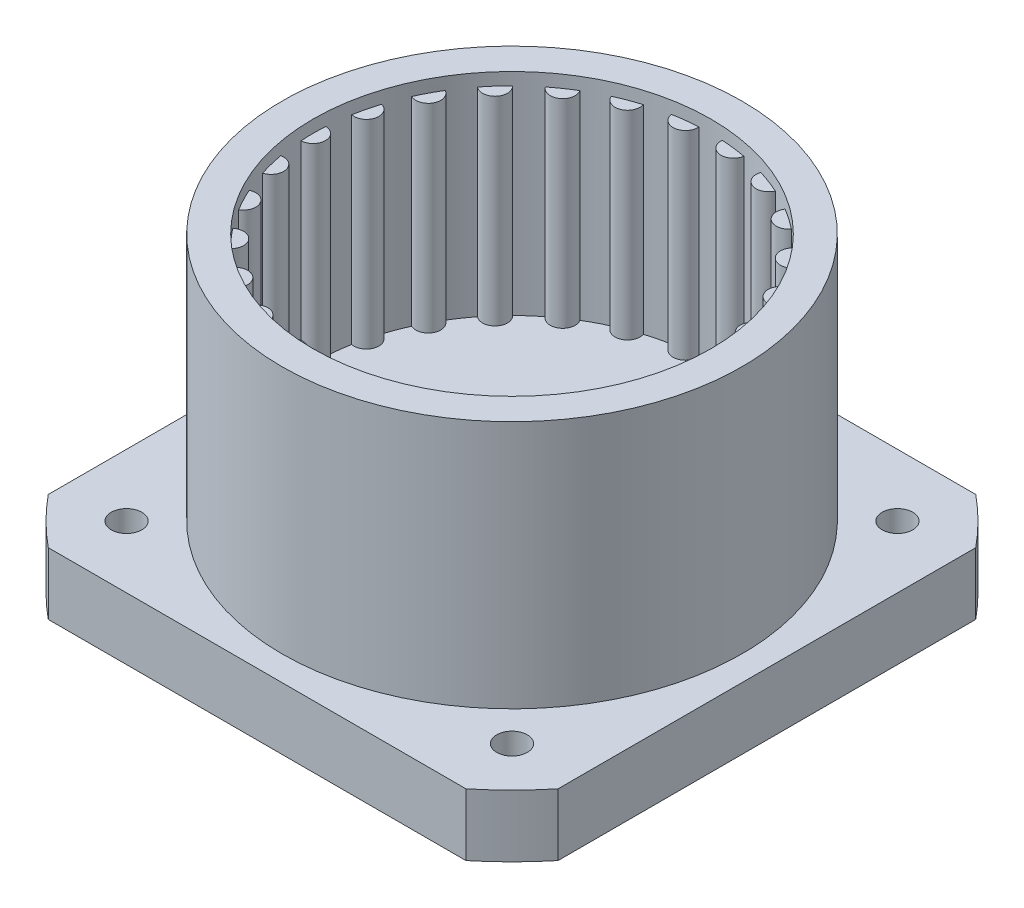
SolidWorks part; units mm, degrees
ref_plane "Front Plane" through (0, 0, 0) normal (0, 0, 1) x (1, 0, 0)
ref_plane "Top Plane" through (0, 0, 0) normal (0, 1, 0) x (1, 0, 0)
ref_plane "Right Plane" through (0, 0, 0) normal (1, 0, 0) x (0, 0, -1)
sketch "Sketch1" plane through (0, 0, 0) normal (0, 1, 0) x (1, 0, 0)
  circle A0 centre (15.5, 0) radius 1
  circle A1 centre (15.0351, -3.8291) radius 1
  circle A2 centre (13.6673, -7.4356) radius 1
  circle A3 centre (11.4762, -10.61) radius 1
  circle A4 centre (8.589, -13.1677) radius 1
  circle A5 centre (5.1737, -14.9603) radius 1
  circle A6 centre (1.4286, -15.8833) radius 1
  circle A7 centre (-2.4286, -15.8833) radius 1
  circle A8 centre (-6.1737, -14.9603) radius 1
  circle A9 centre (-9.589, -13.1677) radius 1
  circle A10 centre (-12.4762, -10.61) radius 1
  circle A11 centre (-14.6673, -7.4356) radius 1
  circle A12 centre (-16.0351, -3.8291) radius 1
  circle A13 centre (-16.5, 0) radius 1
  circle A14 centre (-16.0351, 3.8291) radius 1
  circle A15 centre (-14.6673, 7.4356) radius 1
  circle A16 centre (-12.4762, 10.61) radius 1
  circle A17 centre (-9.589, 13.1677) radius 1
  circle A18 centre (-6.1737, 14.9603) radius 1
  circle A19 centre (-2.4286, 15.8833) radius 1
  circle A20 centre (1.4286, 15.8833) radius 1
  circle A21 centre (5.1737, 14.9603) radius 1
  circle A22 centre (8.589, 13.1677) radius 1
  circle A23 centre (11.4762, 10.61) radius 1
  circle A24 centre (13.6673, 7.4356) radius 1
  circle A25 centre (15.0351, 3.8291) radius 1
  spline S0 degree 4 number of poles 315 (14.4, 0) -> (-15.4, 0) construction
sketch "Sketch2" plane through (0, 0, 0) normal (0, 1, 0) x (1, 0, 0)
  circle A0 centre (15.5, 0) radius 1
  circle A1 centre (15.0351, -3.8291) radius 1
  circle A2 centre (13.6673, -7.4356) radius 1
  circle A3 centre (11.4762, -10.61) radius 1
  circle A4 centre (8.589, -13.1677) radius 1
  circle A5 centre (5.1737, -14.9603) radius 1
  circle A6 centre (1.4286, -15.8833) radius 1
  circle A7 centre (-2.4286, -15.8833) radius 1
  circle A8 centre (-6.1737, -14.9603) radius 1
  circle A9 centre (-9.589, -13.1677) radius 1
  circle A10 centre (-12.4762, -10.61) radius 1
  circle A11 centre (-14.6673, -7.4356) radius 1
  circle A12 centre (-16.0351, -3.8291) radius 1
  circle A13 centre (-16.5, 0) radius 1
  circle A14 centre (-16.0351, 3.8291) radius 1
  circle A15 centre (-14.6673, 7.4356) radius 1
  circle A16 centre (-12.4762, 10.61) radius 1
  circle A17 centre (-9.589, 13.1677) radius 1
  circle A18 centre (-6.1737, 14.9603) radius 1
  circle A19 centre (-2.4286, 15.8833) radius 1
  circle A20 centre (1.4286, 15.8833) radius 1
  circle A21 centre (5.1737, 14.9603) radius 1
  circle A22 centre (8.589, 13.1677) radius 1
  circle A23 centre (11.4762, 10.61) radius 1
  circle A24 centre (13.6673, 7.4356) radius 1
  circle A25 centre (15.0351, 3.8291) radius 1
extrude "Boss-Extrude1" add sketch "Sketch2" along normal blind 8 and the other way blind 8
sketch "Sketch4" plane through (0, 0, 0) normal (0, 1, 0) x (1, 0, 0)
  line L0 (-15.4, 0) -> (14.4, 0) construction
  line L1 (0, 0) -> (0, 14.9128) construction
  line L2 (0, 0) -> (0, -14.9128) construction
  line L3 (0, 0) -> (-0.5, 0) construction
  line L4 (-0.5, 0) -> (-0.5, 15.3103) construction
  line L5 (-0.5, 0) -> (-0.5, -15.3103) construction
  line L6 (14.4, 0) -> (15.5, 0) construction
  line L7 (0, 0) -> (10, 0) construction
  line L8 (7.9, 0) -> (9.5, 0)
  line L9 (-0.5, 0) -> (9.5, 0) construction
  line L10 (-0.5, 15.3103) -> (-0.5, -15.3103) construction
  circle A0 centre (-0.5, 0) radius 16
  circle A1 centre (15.5, 0) radius 1
  circle A2 centre (15.0351, -3.8291) radius 1
  circle A3 centre (13.6673, -7.4356) radius 1
  circle A4 centre (11.4762, -10.61) radius 1
  circle A5 centre (8.589, -13.1677) radius 1
  circle A6 centre (5.1737, -14.9603) radius 1
  circle A7 centre (1.4286, -15.8833) radius 1
  circle A8 centre (-2.4286, -15.8833) radius 1
  circle A9 centre (-6.1737, -14.9603) radius 1
  circle A10 centre (-9.589, -13.1677) radius 1
  circle A11 centre (-12.4762, -10.61) radius 1
  circle A12 centre (-14.6673, -7.4356) radius 1
  circle A13 centre (-16.0351, -3.8291) radius 1
  circle A14 centre (-16.5, 0) radius 1
  circle A15 centre (-16.0351, 3.8291) radius 1
  circle A16 centre (-14.6673, 7.4356) radius 1
  circle A17 centre (-12.4762, 10.61) radius 1
  circle A18 centre (-9.589, 13.1677) radius 1
  circle A19 centre (-6.1737, 14.9603) radius 1
  circle A20 centre (-2.4286, 15.8833) radius 1
  circle A21 centre (1.4286, 15.8833) radius 1
  circle A22 centre (5.1737, 14.9603) radius 1
  circle A23 centre (8.589, 13.1677) radius 1
  circle A24 centre (11.4762, 10.61) radius 1
  circle A25 centre (13.6673, 7.4356) radius 1
  circle A26 centre (15.0351, 3.8291) radius 1
  circle A27 centre (0, 0) radius 10
  circle A28 centre (10, 0) radius 2.1
  circle A29 centre (5, -8.6603) radius 2.1
  circle A30 centre (-5, -8.6603) radius 2.1
  circle A31 centre (-10, 0) radius 2.1
  circle A32 centre (-5, 8.6603) radius 2.1
  circle A33 centre (5, 8.6603) radius 2.1
  circle A34 centre (-6, 8.6603) radius 2.1
  circle A35 centre (4, 8.6603) radius 2.1
  circle A36 centre (9, 0) radius 2.1
  circle A37 centre (4, -8.6603) radius 2.1
  circle A38 centre (-6, -8.6603) radius 2.1
  circle A39 centre (-1, 0) radius 10
  circle A40 centre (-11, 0) radius 2.1
  circle A41 centre (9.5, 0) radius 1.5
  circle A42 centre (4.5, -8.6603) radius 1.5
  circle A43 centre (-5.5, -8.6603) radius 1.5
  circle A44 centre (-10.5, 0) radius 1.5
  circle A45 centre (-5.5, 8.6603) radius 1.5
  circle A46 centre (4.5, 8.6603) radius 1.5
  circle A47 centre (-0.5, 0) radius 19.5
  circle A48 centre (0, 0) radius 5.55
  circle A49 centre (-0.5, 0) radius 5.55
  spline S0 degree 4 number of poles 369 (14.1521, 3.1658) -> (-14.9531, 3.4358) construction
  spline S1 degree 4 number of poles 315 (14.4, 0) -> (-15.4, 0)
  spline S2 degree 4 number of poles 315 (14.4, 0) -> (-15.4, 0)
  spline S3 degree 4 number of poles 315 (-15.4, 0) -> (14.4, 0)
  spline S4 degree 4 number of poles 315 (-15.4, 0) -> (14.4, 0)
  dimension "D1" = 32
  dimension "D2" = 2
  dimension "D4" = 20
  dimension "D5" = 4.2
  dimension "D8" = 6
  dimension "D7" = 10
  dimension "D9" = 10
  dimension "D3" = 26
  dimension "D6" = 6
sketch "Sketch5" plane through (0, 0, 0) normal (0, 1, 0) x (1, 0, 0)
  circle A0 centre (-0.5, 0) radius 16
  circle A1 centre (-0.5, 0) radius 18.5
extrude "Boss-Extrude3" add sketch "Sketch5" along normal blind 8 and the other way blind 8
sketch "Sketch6" plane through (0, 8, 0) normal (0, 1, 0) x (1, 0, 0)
  circle A0 centre (-0.5, 0) radius 18.5 construction
  circle A1 centre (-0.5, 0) radius 18.5
  circle A2 centre (-0.5, 0) radius 16
  dimension "D1" = 37
  dimension "D2" = 32
extrude "Boss-Extrude4" add sketch "Sketch6" along normal blind 1
sketch "Sketch7" plane through (0, 9, 0) normal (0, 1, 0) x (1, 0, 0)
  circle A0 centre (-0.5, 0) radius 18.5 construction
  circle A1 centre (-5.5, -8.6603) radius 1.5 construction
  circle A2 centre (4.5, -8.6603) radius 1.5 construction
  circle A3 centre (9.5, 0) radius 1.5 construction
  circle A4 centre (-10.5, 0) radius 1.5 construction
  circle A5 centre (-5.5, 8.6603) radius 1.5 construction
  circle A6 centre (4.5, 8.6603) radius 1.5 construction
  circle A7 centre (-0.5, 0) radius 18.5
  circle A8 centre (-5.5, -8.6603) radius 1.5
  circle A9 centre (4.5, -8.6603) radius 1.5
  circle A10 centre (9.5, 0) radius 1.5
  circle A11 centre (-10.5, 0) radius 1.5
  circle A12 centre (-5.5, 8.6603) radius 1.5
  circle A13 centre (4.5, 8.6603) radius 1.5
sketch "Sketch8" plane through (0, -8, 0) normal (0, -1, 0) x (1, 0, 0)
  circle A0 centre (-0.5, 0) radius 18.5
  dimension "D1" = 37
extrude "Boss-Extrude5" add sketch "Sketch8" along normal blind 3
sketch "Sketch9" plane through (0, -11, 0) normal (0, -1, 0) x (1, 0, 0)
  circle A0 centre (-0.5, 0) radius 6
  dimension "D1" = 12
extrude "Cut-Extrude1" cut sketch "Sketch9" against normal blind 3
ref_plane "Plane1" through (13.1751, 8, 8.3061) normal (0, -1, 0) x (-1, 0, 0)
sketch "Sketch13" plane through (0, -11, 0) normal (0, -1, 0) x (1, 0, 0)
  line L4 (-17.2929, -20.5) -> (16.2929, -20.5)
  line L5 (-21, 16.7929) -> (-21, -16.7929)
  line L6 (16.2929, 20.5) -> (-17.2929, 20.5)
  line L7 (20, -16.7929) -> (20, 16.7929)
  line L8 (-17.2929, -20.5) -> (16.2929, -20.5)
  line L9 (-21, 16.7929) -> (-21, -16.7929)
  line L10 (16.2929, 20.5) -> (-17.2929, 20.5)
  line L11 (20, -16.7929) -> (20, 16.7929)
  circle A0 centre (-16, -15.5) radius 1.23 construction
  circle A1 centre (15, -15.5) radius 1.23 construction
  circle A2 centre (15, 15.5) radius 1.23 construction
  circle A3 centre (-16, 15.5) radius 1.23 construction
  arc A4 (-21, -16.7929) -> (-17.2929, -20.5) centre (-0.5, 0) ccw
  arc A5 (-17.2929, 20.5) -> (-21, 16.7929) centre (-0.5, 0) ccw
  arc A6 (20, 16.7929) -> (16.2929, 20.5) centre (-0.5, 0) ccw
  arc A7 (16.2929, -20.5) -> (20, -16.7929) centre (-0.5, 0) ccw
  arc A8 (-21, -16.7929) -> (-17.2929, -20.5) centre (-0.5, 0) ccw
  arc A9 (-17.2929, 20.5) -> (-21, 16.7929) centre (-0.5, 0) ccw
  arc A10 (20, 16.7929) -> (16.2929, 20.5) centre (-0.5, 0) ccw
  arc A11 (16.2929, -20.5) -> (20, -16.7929) centre (-0.5, 0) ccw
  circle A12 centre (-16, -15.5) radius 1.23
  circle A13 centre (15, -15.5) radius 1.23
  circle A14 centre (15, 15.5) radius 1.23
  circle A15 centre (-16, 15.5) radius 1.23
  circle A16 centre (-0.5, 0) radius 6
  dimension "D1" = 0
extrude "Boss-Extrude7" add sketch "Sketch13" along normal blind 5
